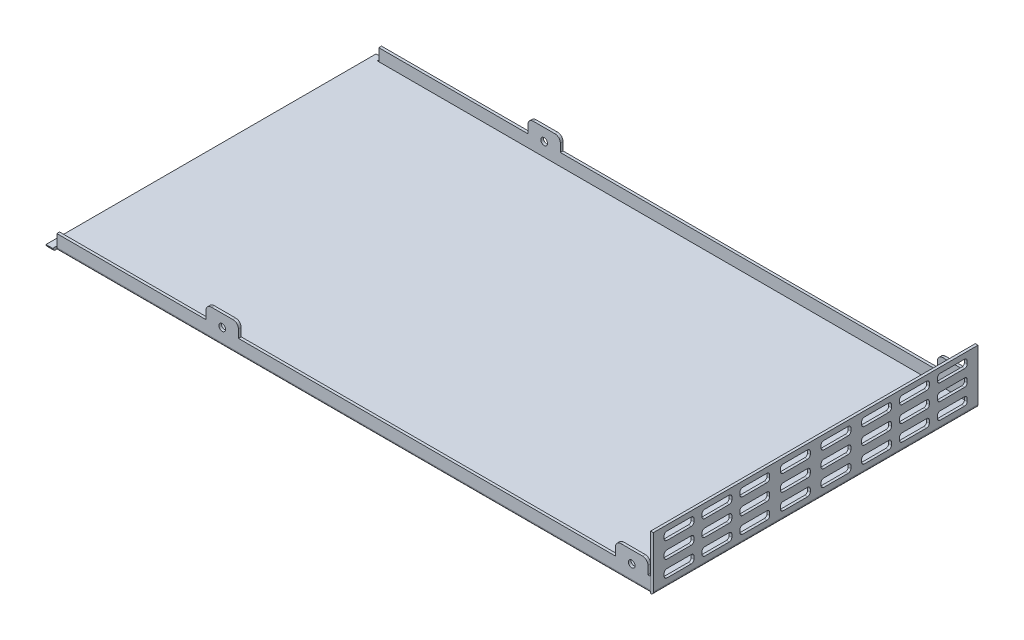
SolidWorks part; units mm, degrees
ref_plane "Front Plane" through (0, 0, 0) normal (0, 0, 1) x (1, 0, 0)
ref_plane "Top Plane" through (0, 0, 0) normal (0, 1, 0) x (1, 0, 0)
ref_plane "Right Plane" through (0, 0, 0) normal (1, 0, 0) x (0, 0, -1)
sketch "Sketch1" plane through (0, 0, 0) normal (0, 1, 0) x (1, 0, 0)
  line L0 (223.5, -60) -> (223.5, 60)
  line L1 (0, -61) -> (2.5, -61)
  line L2 (0, -61) -> (0, 61)
  line L3 (0, 61) -> (2.5, 61)
  line L4 (2.5, -61) -> (2.5, -60)
  line L5 (0, -61) -> (2.5, 61) construction
  line L6 (0, 61) -> (2.5, -61) construction
  line L10 (2.5, -60) -> (223.5, -60)
  line L11 (2.5, 60) -> (223.5, 60)
  line L12 (223.5, -61) -> (223.5, 61) construction
  line L13 (2.5, 60) -> (2.5, 61)
  point P10 (0, 60)
  point P12 (0, -60)
  dimension "D1" = 122
  dimension "D2" = 2.5
extrude "Boss-Extrude1" add sketch "Sketch1" along normal blind 1
sketch "Sketch2" plane through (0, 1, 0) normal (0, 1, 0) x (1, 0, 0)
  line L0 (2.5, -60) -> (223.5, -60) construction
  line L1 (223.5, 60) -> (222.5, 60)
  line L2 (223.5, 60) -> (223.5, -60)
  line L3 (223.5, -60) -> (222.5, -60)
  line L4 (222.5, 60) -> (222.5, -60)
  dimension "D1" = 1
extrude "Boss-Extrude2" add sketch "Sketch2" along normal blind 19
sketch "Sketch3" plane through (0, 0, 60) normal (0, 0, 1) x (1, 0, 0)
  line L1 (219.5, 10.5) -> (211.5, 10.5)
  line L2 (222.5, 5.5) -> (222.5, 1)
  line L3 (222.5, 1) -> (3, 1)
  line L4 (3, 5.5) -> (3, 1)
  line L5 (2.5, 1) -> (222.5, 1) construction
  line L6 (2.5, 0) -> (223.5, 0) construction
  line L7 (0, 1) -> (0, 0) construction
  line L8 (58.13, 8.5) -> (58.13, 5.5)
  line L9 (70.13, 8.5) -> (70.13, 5.5)
  line L10 (209.5, 8.5) -> (209.5, 5.5)
  line L11 (221.5, 8.5) -> (221.5, 5.5)
  line L12 (222.5, 5.5) -> (221.5, 5.5)
  line L13 (209.5, 5.5) -> (70.13, 5.5)
  line L14 (222.5, 10.5) -> (3, 10.5) construction
  line L15 (221.5, 10.5) -> (221.5, 1) construction
  line L16 (68.13, 10.5) -> (60.13, 10.5)
  line L17 (222.5, 5.5) -> (3, 5.5) construction
  line L18 (209.5, 10.5) -> (209.5, 1) construction
  line L19 (58.13, 5.5) -> (3, 5.5)
  line L21 (70.13, 10.5) -> (70.13, 1) construction
  line L22 (58.13, 10.5) -> (58.13, 1) construction
  line L23 (3, 10.5) -> (3, 1) construction
  arc A0 (60.13, 10.5) -> (58.13, 8.5) centre (60.13, 8.5) ccw
  arc A1 (70.13, 8.5) -> (68.13, 10.5) centre (68.13, 8.5) ccw
  arc A2 (219.5, 10.5) -> (221.5, 8.5) centre (219.5, 8.5) cw
  arc A3 (209.5, 8.5) -> (211.5, 10.5) centre (211.5, 8.5) cw
  dimension "D8" = 2
  dimension "D9" = 2
  dimension "D10" = 2
  dimension "D11" = 2
  dimension "D1" = 10.5
  dimension "D2" = 3
  dimension "D3" = 55.13
  dimension "D4" = 12
  dimension "D5" = 139.37
  dimension "D6" = 12
  dimension "D7" = 5
extrude "Boss-Extrude3" add sketch "Sketch3" against normal blind 1
hole_wizard "M3x0.5 Tapped Hole1" positions "Sketch5" profile "Sketch4" tap size "M3x0.5" standard "ANSI Metric"
sketch "Sketch5" plane through (0, 0, 60) normal (0, 0, 1) x (1, 0, 0)
  line L0 (2.5, 0) -> (223.5, 0) construction
  line L1 (58.13, 8.5) -> (58.13, 5.5) construction
  line L3 (209.5, 8.5) -> (209.5, 5.5) construction
  point P0 (64.13, 6)
  point P5 (58.13, 7)
  point P8 (215.5, 6)
  dimension "D1" = 6
  dimension "D2" = 6
  dimension "D3" = 6
  dimension "D4" = 6
sketch "Sketch4" plane through (64.13, 6, 60) normal (1, 0, 0) x (0, -1, 0)
  line L0 (0, 0) -> (0, 1.7511)
  line L1 (0, 1.7511) -> (1.25, 1)
  line L2 (1.25, 1) -> (1.25, 0)
  line L5 (1.25, 0) -> (0, 0)
  line L10 (0, 1.7511) -> (-1.25, 1) construction
  line L11 (0, -6.35) -> (0, 107.95) construction
  dimension "Tap Drill Dia." = 2.5
  dimension "Tap Drill Depth" = 1
  dimension "Drill Angle" = 118
cosmetic thread "Hole Thread1" parameters "D1"=1, "D2"=3
cosmetic thread "Hole Thread2" parameters "D1"=1, "D2"=3
mirror "Mirror5" about plane through (0, 0, 0) normal (0, 0, 1) of "M3x0.5 Tapped Hole1", "Boss-Extrude3"
sketch "Sketch6" plane through (0, 0, 60) normal (0, 0, 1) x (1, 0, 0)
  line L0 (2.5, 0) -> (223.5, 0) construction
  line L1 (222.5, 5.5) -> (222.4, 5.5)
  line L2 (222.5, 5.5) -> (222.5, 0)
  line L3 (222.5, 0) -> (222.4, 0)
  line L4 (222.4, 5.5) -> (222.4, 0)
  dimension "D1" = 0
  dimension "D2" = 0.1
extrude "Cut-Extrude1" cut sketch "Sketch6" against normal blind 1
mirror "Mirror6" about plane through (0, 0, 0) normal (0, 0, 1) of "Cut-Extrude1"
sketch "Sketch7" plane through (0, 0, 60) normal (0, 0, 1) x (1, 0, 0)
  line L1 (3, 1) -> (2.5, 1)
  line L2 (3, 1) -> (3, 0)
  line L3 (3, 0) -> (2.5, 0)
  line L4 (2.5, 1) -> (2.5, 0)
extrude "Cut-Extrude2" cut sketch "Sketch7" against normal blind 1
mirror "Mirror7" about plane through (0, 0, 0) normal (0, 0, 1) of "Cut-Extrude2"
fillet "Fillet2" radius 1 1 edges at (223.5, 0, 0)
fillet "Fillet11" radius 1 2 edges at (112.7, 0, -60) (112.7, 0, 60)
sketch "Sketch8" plane through (223.5, 0, 0) normal (1, 0, 0) x (0, 0, -1)
  line L0 (59, 0) -> (-59, 0) construction
  line L1 (-55, 6) -> (-46, 6)
  line L2 (-56, 5) -> (-56, 4)
  line L3 (-55, 3) -> (-46, 3)
  line L4 (-45, 5) -> (-45, 4)
  line L5 (-60, 20) -> (-60, 1) construction
  arc A0 (-55, 6) -> (-56, 5) centre (-55, 5) ccw
  arc A1 (-45, 5) -> (-46, 6) centre (-46, 5) ccw
  arc A2 (-46, 3) -> (-45, 4) centre (-46, 4) ccw
  arc A3 (-56, 4) -> (-55, 3) centre (-55, 4) ccw
  point P10 (-56, 6)
  point P15 (-45, 3)
  point P18 (-56, 3)
  dimension "D5" = 1
  dimension "D6" = 1
  dimension "D7" = 1
  dimension "D8" = 1
  dimension "D1" = 3
  dimension "D2" = 11
  dimension "D3" = 3
  dimension "D4" = 4
extrude "Cut-Extrude3" cut sketch "Sketch8" against normal blind 1
pattern_linear "LPattern1" count 3 spacing 14 along (0, 0, -1) count 3 spacing 6 along (0, 1, 0) of "Cut-Extrude3"
mirror "Mirror8" about plane through (0, 0, 0) normal (0, 0, 1) of "LPattern1"
sketch "Sketch9" plane through (223.5, 0, 0) normal (1, 0, 0) x (0, 0, -1)
  line L0 (-17, 16) -> (-17, 17) construction
  line L1 (-12, 18) -> (-3, 18)
  line L2 (-13, 17) -> (-13, 16)
  line L3 (-12, 15) -> (-3, 15)
  line L4 (-2, 17) -> (-2, 16)
  line L5 (3, 18) -> (12, 18)
  line L6 (2, 17) -> (2, 16)
  line L7 (3, 15) -> (12, 15)
  line L8 (13, 17) -> (13, 16)
  line L9 (17, 16) -> (17, 17) construction
  arc A0 (-12, 18) -> (-13, 17) centre (-12, 17) ccw
  arc A1 (-2, 17) -> (-3, 18) centre (-3, 17) ccw
  arc A2 (-3, 15) -> (-2, 16) centre (-3, 16) ccw
  arc A3 (-13, 16) -> (-12, 15) centre (-12, 16) ccw
  arc A4 (3, 18) -> (2, 17) centre (3, 17) ccw
  arc A5 (13, 17) -> (12, 18) centre (12, 17) ccw
  arc A6 (12, 15) -> (13, 16) centre (12, 16) ccw
  arc A7 (2, 16) -> (3, 15) centre (3, 16) ccw
  point P14 (-13, 18)
  point P17 (-2, 18)
  point P20 (-2, 15)
  point P25 (2, 18)
  point P28 (13, 18)
  point P33 (2, 15)
  dimension "D7" = 1
  dimension "D8" = 1
  dimension "D9" = 1
  dimension "D10" = 1
  dimension "D11" = 1
  dimension "D12" = 1
  dimension "D13" = 1
  dimension "D14" = 1
  dimension "D1" = 4
  dimension "D2" = 11
  dimension "D3" = 4
  dimension "D4" = 11
  dimension "D5" = 3
  dimension "D6" = 3
extrude "Cut-Extrude4" cut sketch "Sketch9" against normal blind 1
pattern_linear "LPattern2" count 3 spacing 6 along (0, -1, 0) of "Cut-Extrude4"
fillet "Fillet12" radius 1 2 edges at (1.25, 0, 61) (1.25, 0, -61)
